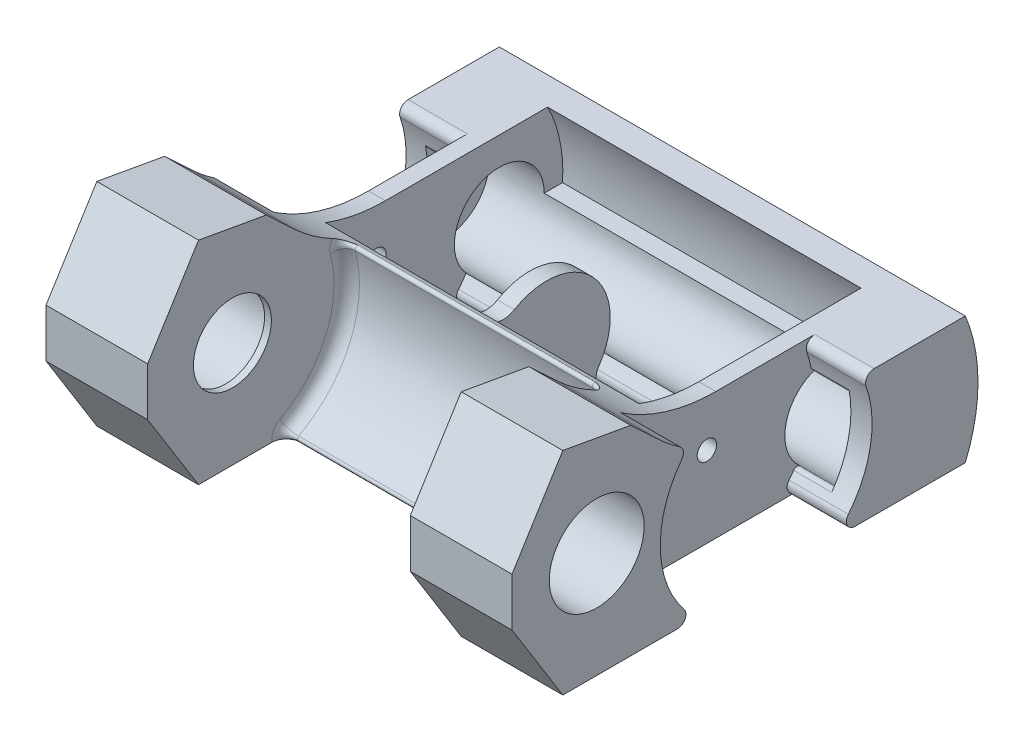
SolidWorks part; units mm, degrees
ref_plane "Front Plane" through (0, 0, 0) normal (0, 0, 1) x (1, 0, 0)
ref_plane "Top Plane" through (0, 0, 0) normal (0, 1, 0) x (1, 0, 0)
ref_plane "Right Plane" through (0, 0, 0) normal (1, 0, 0) x (0, 0, -1)
sketch "Sketch2" plane through (0, 0, 0) normal (1, 0, 0) x (0, 0, -1)
  line L0 (-8, -25) -> (87, -25)
  line L1 (-8, -25) -> (-20, -5.7143)
  line L2 (-20, -5.7143) -> (-20, 5.7143)
  line L3 (-20, 5.7143) -> (-8, 25)
  line L4 (-8, 25) -> (8, 22.1448)
  line L5 (8, 22.1448) -> (14.7837, 15.7957)
  line L6 (42.117, 5) -> (87, 5)
  line L7 (8, 22.1448) -> (112.0201, 3.5826) construction
  line L8 (12.5958, -28) -> (77.9204, -28) construction
  line L9 (0, 0) -> (14.7837, 15.7957) construction
  arc A0 (87, 5) -> (87, -25) centre (51, -10) cw
  circle A1 centre (0, 0) radius 11.2
  arc A2 (10.198, -25) -> (25.6047, 8.5673) centre (0, 0) ccw
  circle A3 centre (40, -5.9569) radius 22.0431
  arc A4 (42.117, 5) -> (14.7837, 15.7957) centre (42.117, 45) cw
  point P5 (-20, 0)
  point P17 (90, -10)
  point P20 (0, 23.5724)
  dimension "D1" = 25
  dimension "D2" = 22.4
  dimension "D6" = 3
  dimension "D10" = 3
  dimension "D8" = 27
  dimension "D13" = 40
  dimension "D14" = 44.0863
  dimension "D3" = 20
  dimension "D4" = 20
  dimension "D5" = 8
  dimension "D7" = 30
  dimension "D9" = 110
  dimension "D11" = 3
  dimension "D12" = 40
extrude "Boss-Extrude2" add sketch "Sketch2" along normal mid plane 110 contours A3 L5 L4 L3 L2 L1 L0 A2 A1 | A1 | L5 A3 A2 | A2 A3 L0 L6 | A3 A2 L0 | A3 L0 A0 L6 region at (0, -15.005, 13.434) region at (0, -22.5758, -20.1125) region at (0, -9.5208, -42.2595) region at (0, -3.4404, -22.5258) region at (0, -10.5796, -74.2329) region at (0, 0, 0)
extrude "Cut-Extrude1" cut sketch "Sketch2<3>" against normal mid plane 62 contours A3 L5 L4 L3 L2 L1 L0 A2 A1 | A1 | L5 A3 A2 region at (0, -15.005, 13.434) region at (0, -3.4404, -22.5258) region at (0, 0, 0)
sketch "Sketch2<3>" plane through (0, 0, 0) normal (1, 0, 0) x (0, 0, -1) same geometry as "Sketch2"
extrude "Cut-Extrude2" cut sketch "Sketch2<4>" against normal through all both and the other way through all from offset 0 contours A1 region at (0, 0, 0)
sketch "Sketch2<4>" plane through (0, 0, 0) normal (1, 0, 0) x (0, 0, -1) same geometry as "Sketch2"
sketch "Sketch3" plane through (-31, 0, 0) normal (1, 0, 0) x (0, 0, -1)
  circle A0 centre (0, 0) radius 11.2
  circle A1 centre (0, 0) radius 9.2
  dimension "D1" = 22.4
  dimension "D2" = 2
extrude "Boss-Extrude3" add sketch "Sketch3" against normal blind 1.6
mirror "Mirror1" about plane through (0, 0, 0) normal (1, 0, 0) of "Boss-Extrude3"
sketch "Sketch4" plane through (55, 0, 0) normal (1, 0, 0) x (0, 0, -1)
  circle A0 centre (40, -5.9569) radius 25
  dimension "D1" = 50
extrude "Cut-Extrude3" cut sketch "Sketch4" against normal blind 14
mirror "Mirror2" about plane through (0, 0, 0) normal (1, 0, 0) of "Cut-Extrude3"
fillet "Fillet2" radius 2 8 edges at (-48, 5, -62.471) (-48, -25, -56.1975) (-48, -25, -23.8025) (-48, 10.7705, -21.4206) (48, -25, -56.1975) (48, 5, -62.471) (48, -25, -23.8025) (48, 10.7705, -21.4206)
fillet "Fillet3" radius 0.6 2 edges at (0, 8.5673, -25.6047) (0, -25, -10.198)
fillet "Fillet4" radius 3 6 edges at (31, -24.5445, -12.3173) (31, 7.9465, -26.1635) (-31, -24.5445, -12.3173) (-31, 7.9465, -26.1635) (31, -10.6305, -24.8192) (-31, -10.6305, -24.8192)
sketch "Sketch5" plane through (0, 0, 0) normal (1, 0, 0) x (0, 0, -1)
  line L0 (60.9412, -25) -> (87, -25) construction
  line L1 (19.0588, -25) -> (60.9412, -25) construction
  line L2 (42.117, 5) -> (65.4711, 5) construction
  line L3 (65.4711, 5) -> (87, 5) construction
  line L4 (42.117, 5) -> (65.4711, 5)
  line L5 (65.4711, 5) -> (80.3939, 5)
  line L6 (34.3467, -23.4) -> (81.1569, -23.4)
  circle A0 centre (69, -12.2) radius 10.6 construction
  arc A2 (59.39, -21.7375) -> (63.5843, 2.3365) centre (40, -5.9569) ccw construction
  circle A3 centre (43, -9) radius 15 construction
  arc A4 (19.5739, 11.9575) -> (42.117, 5) centre (42.117, 45) ccw construction
  arc A5 (27.9927, 7.5767) -> (42.117, 5) centre (42.117, 45) ccw
  arc A7 (26.4505, -11.8901) -> (34.3467, -23.4) centre (43, -9) ccw
  arc A8 (13.5539, -25.6377) -> (27.9094, 7.8783) centre (0, 0) ccw
  arc A9 (26.4505, -11.8901) -> (27.9927, 7.5767) centre (0, 0) ccw
  arc A12 (81.4615, -22.6923) -> (81.4615, 2.6923) centre (51, -10) ccw
  arc A13 (81.1569, -23.4) -> (80.3939, 5) centre (51, -10) ccw
  dimension "D1" = 21.2
  dimension "D2" = 12.8
  dimension "D3" = 29
  dimension "D4" = 30
  dimension "D8" = 1.8
  dimension "D5" = 16
  dimension "D6" = 43
  dimension "D9" = 1.6
  dimension "D7" = 2
  dimension "D10" = 6
extrude "Cut-Extrude4" cut sketch "Sketch5" along normal mid plane 74
sketch "Sketch6" plane through (41, 0, 0) normal (1, 0, 0) x (0, 0, -1)
  circle A0 centre (40, -5.9569) radius 2.286
  arc A1 (20.0433, 9.1007) -> (20.61, -21.7375) centre (40, -5.9569) ccw construction
  dimension "D1" = 4.572
extrude "Cut-Extrude5" cut sketch "Sketch6" against normal through all
sketch "Sketch7" plane through (0, 0, 0) normal (1, 0, 0) x (0, 0, -1)
  line L0 (79.6, -12.2) -> (83.9266, -12.2)
  line L1 (34.3467, -23.4) -> (81.1569, -23.4) construction
  line L2 (58.9816, -23.4) -> (81.1569, -23.4)
  arc A0 (61.1364, -19.308) -> (79.6, -12.2) centre (69, -12.2) ccw
  circle A1 centre (69, -12.2) radius 10.6 construction
  arc A2 (81.1569, -23.4) -> (80.3939, 5) centre (51, -10) ccw construction
  arc A3 (59.39, -21.7375) -> (63.5843, 2.3365) centre (40, -5.9569) ccw construction
  arc A4 (59.39, -21.7375) -> (60.9412, -25) centre (60.9412, -23) ccw construction
  arc A5 (59.39, -21.7375) -> (61.1364, -19.308) centre (40, -5.9569) ccw
  arc A6 (59.39, -21.7375) -> (58.9816, -23.4) centre (60.9412, -23) ccw
  arc A7 (81.1569, -23.4) -> (83.9266, -12.2) centre (51, -10) ccw
extrude "Boss-Extrude4" add sketch "Sketch7" along normal mid plane 110
sketch "Sketch9" plane through (0, 0, 0) normal (1, 0, 0) x (0, 0, -1)
  circle A0 centre (69, -12.2) radius 10.6
  arc A1 (61.1364, -19.308) -> (79.6, -12.2) centre (69, -12.2) ccw construction
extrude "Cut-Extrude6" cut sketch "Sketch9" against normal mid plane 100
fillet "Fillet5" radius 1 4 edges at (45.5, -19.308, -61.1364) (45.5, -2.4859, -64.7579) (-45.5, -2.4859, -64.7579) (-45.5, -19.308, -61.1364)
sketch "Sketch10" plane through (0, 0, 0) normal (1, 0, 0) x (0, 0, -1)
  line L0 (34.3467, -23.4) -> (58.9816, -23.4) construction
  line L2 (34.3467, -23.4) -> (58.9816, -23.4)
  arc A0 (55.5558, -16.8915) -> (35.5481, 4.507) centre (43.1907, -8.4) ccw
  arc A1 (26.4505, -11.8901) -> (27.9927, 7.5767) centre (0, 0) ccw construction
  arc A3 (55.5558, -16.8915) -> (58.9816, -23.4) centre (58.9816, -19.2442) ccw
  arc A5 (35.5481, 4.507) -> (27.9927, 7.5767) centre (32.9378, 8.9151) cw
  arc A6 (26.4505, -11.8901) -> (34.3467, -23.4) centre (43, -9) ccw construction
  arc A7 (26.4505, -11.8901) -> (34.3467, -23.4) centre (43, -9) ccw
  arc A8 (26.4505, -11.8901) -> (27.9927, 7.5767) centre (0, 0) ccw
  point P2 (43.0113, -7.5045)
  point P12 (58.9816, -23.4)
  point P14 (27.9927, 7.5767)
  dimension "D1" = 30
extrude "Boss-Extrude5" add sketch "Sketch10" against normal blind 4
